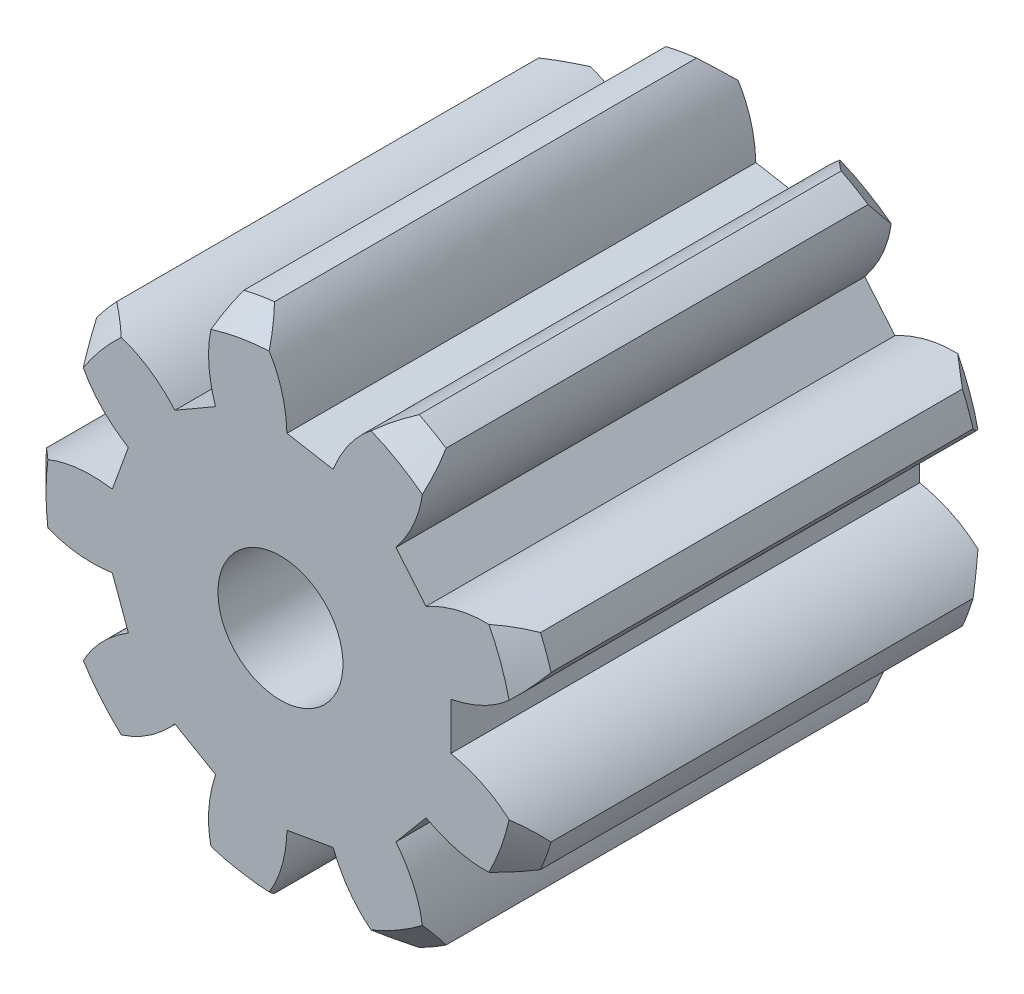
SolidWorks part; units mm, degrees
ref_plane "前视基准面" through (0, 0, 0) normal (0, 0, 1) x (1, 0, 0)
ref_plane "上视基准面" through (0, 0, 0) normal (0, 1, 0) x (1, 0, 0)
ref_plane "右视基准面" through (0, 0, 0) normal (1, 0, 0) x (0, 0, -1)
sketch "草图1" plane through (0, 0, 0) normal (0, 0, 1) x (1, 0, 0)
  circle A0 centre (0, 0) radius 3.3
  dimension "D1" = 6.6
extrude "凸台-拉伸1" add sketch "草图1" along normal blind 6
chamfer "倒角1" distance 0.3 angle 45 2 edges at (3.3, 0, 6) (3.3, 0, 0)
sketch "草图2" plane through (0, 0, 0) normal (0, 0, -1) x (-1, 0, 0)
  line L0 (0, 0) -> (-4.4803, 0) construction
  line L1 (-2.1803, 0.3) -> (-2.1803, -0.3)
  spline S0 degree 2 poles (-2.1803, -0.3) (-3.087, -0.4886) (-3.3803, -1.4) knots 0 0 0 1 1 1
  spline S1 degree 2 poles (-2.1803, 0.3) (-3.087, 0.4886) (-3.3803, 1.4) knots 0 0 0 1 1 1
  spline S2 degree 1 poles (-3.3803, 1.4) (-3.3803, -1.4) knots 0 0 1 1
  dimension "D1" = 0.6
  dimension "D2" = 2.8
  dimension "D3" = 1.2
  dimension "D4" = 1.2
extrude "切除-拉伸1" cut sketch "草图2" against normal through all
ref_axis "基准轴1" through (0, 0, 0) along (0, 0, -1)
pattern_circular "阵列(圆周)1" count 9 every 40 about axis through (0, 0, 0) along (0, 0, -1) of "切除-拉伸1"
sketch "草图3" plane through (0, 0, 0) normal (0, 0, -1) x (-1, 0, 0)
  circle A0 centre (0, 0) radius 0.8
  dimension "D1" = 1.6
extrude "切除-拉伸2" cut sketch "草图3" against normal through all
